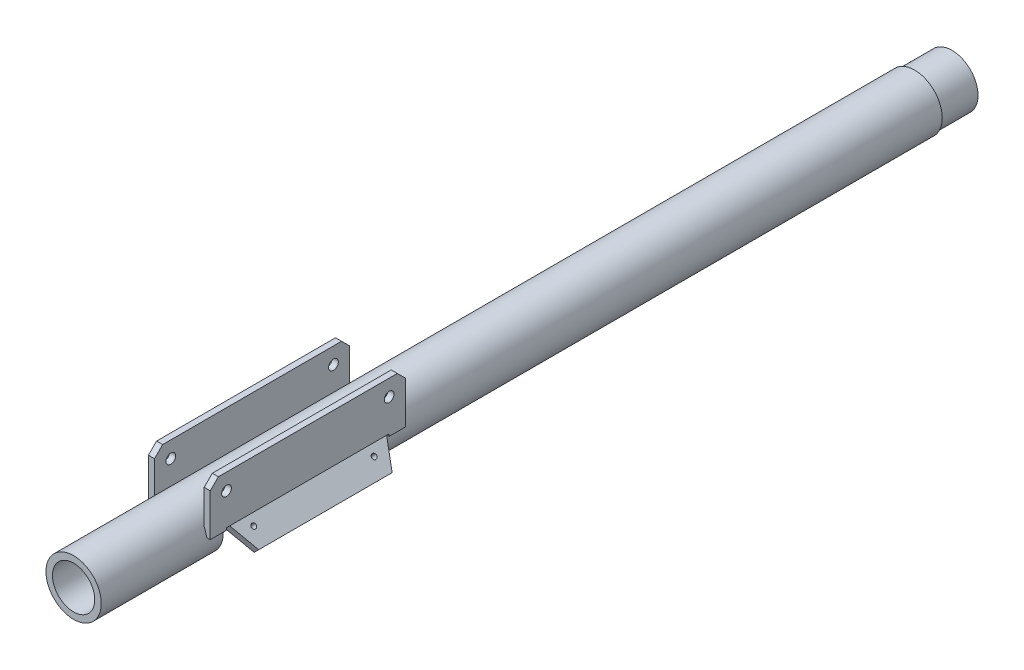
SolidWorks part; units mm, degrees
ref_plane "Front Plane" through (0, 0, 0) normal (0, 0, 1) x (1, 0, 0)
ref_plane "Top Plane" through (0, 0, 0) normal (0, 1, 0) x (1, 0, 0)
ref_plane "Right Plane" through (0, 0, 0) normal (1, 0, 0) x (0, 0, -1)
sketch "Sketch1" plane through (0, 0, 0) normal (0, 0, 1) x (1, 0, 0)
  circle A0 centre (0, 0) radius 17
extrude "Outer Barrel Creation" add sketch "Sketch1" against normal blind 540
sketch "Sketch2" plane through (0, 0, 0) normal (0, 0, 1) x (1, 0, 0)
  circle A0 centre (0, 0) radius 13
sketch "Sketch4" plane through (0, 0, 0) normal (1, 0, 0) x (0, 0, -1)
  line L0 (0, -17) -> (540, -17) construction
  line L1 (75, -17) -> (175, -17)
  line L2 (75, -17) -> (75, 2)
  line L3 (75, 2) -> (175, 2)
  line L4 (175, -17) -> (175, 2)
  line L5 (0, 17) -> (0, -17) construction
  line L6 (540, -17) -> (540, 17) construction
  line L7 (540, 17) -> (0, 17) construction
  point P8 (175, -7.5)
  dimension "D1" = 75
  dimension "D2" = 365
  dimension "D3" = 15
extrude "Screw Intake Extrude" cut sketch "Sketch4" along normal through all both and the other way through all
sketch "Sketch6" plane through (0, 0, 0) normal (1, 0, 0) x (0, 0, -1)
  line L0 (175, 2) -> (175, -17) construction
  line L1 (185, 2.4808) -> (65, 2.4808)
  line L2 (185, 2.4808) -> (185, 7.4808)
  line L3 (185, 7.4808) -> (65, 7.4808)
  line L4 (65, 2.4808) -> (65, 7.4808)
  line L5 (75, -17) -> (75, 2) construction
  dimension "D1" = 10
  dimension "D2" = 5
  dimension "D3" = 10
extrude "Parallel Fin Side Extrusion" add sketch "Sketch6" along normal blind 19 and the other way blind 19
sketch "Sketch7" plane through (0, 7.4808, 0) normal (0, 1, 0) x (1, 0, 0)
  line L1 (15.2656, 185) -> (19, 185)
  line L2 (15.2656, 185) -> (15.2656, 65)
  line L3 (15.2656, 65) -> (19, 65)
  line L4 (19, 185) -> (19, 65)
extrude "Parallel Fin Height Side 1" add sketch "Sketch7" along normal blind 26
sketch "Sketch8" plane through (0, 7.4808, 0) normal (0, 1, 0) x (1, 0, 0)
  line L1 (-19, 185) -> (-15.2656, 185)
  line L2 (-19, 185) -> (-19, 65)
  line L3 (-19, 65) -> (-15.2656, 65)
  line L4 (-15.2656, 185) -> (-15.2656, 65)
extrude "Parallel Fin Height Side 2" add sketch "Sketch8" along normal blind 26
sketch "Sketch9" plane through (-19, 0, 0) normal (-1, 0, 0) x (0, 0, 1)
  line L0 (-185, 33.4808) -> (-65, 33.4808) construction
  line L1 (-185, 2.4808) -> (-185, 33.4808) construction
  line L2 (-65, 33.4808) -> (-65, 2.4808) construction
  line L3 (-180, 33.4808) -> (-185, 28.4808)
  line L4 (-70, 33.4808) -> (-65, 28.4808)
  line L5 (-185, 28.4808) -> (-185, 33.4808)
  line L6 (-185, 33.4808) -> (-180, 33.4808)
  line L7 (-65, 28.4808) -> (-65, 33.4808)
  line L8 (-65, 33.4808) -> (-70, 33.4808)
  circle A0 centre (-175, 23.4808) radius 3
  circle A1 centre (-75, 23.4808) radius 3
  dimension "D5" = 6
  dimension "D6" = 6
  dimension "D1" = 10
  dimension "D2" = 10
  dimension "D3" = 10
  dimension "D4" = 10
  dimension "D7" = 5
  dimension "D8" = 5
  dimension "D9" = 5
  dimension "D10" = 5
extrude "Parallel Fin Details" cut sketch "Sketch9" against normal through all
extrude "Inner Barrel Extrusion" cut sketch "Sketch2" against normal through all
sketch "Sketch10" plane through (0, 0, 0) normal (1, 0, 0) x (0, 0, -1)
  line L0 (0, 0) -> (540, 0)
  line L1 (540, -13) -> (540, 13) construction
ref_axis "Axis1" through (0, 0, 0) along (0, 0, -1)
ref_plane "Plane1" through (0, 0, 0) normal (0.7071, 0.7071, 0) x (0, 0, -1)
sketch "Sketch11" plane through (0, 0, 0) normal (0.7071, 0.7071, 0) x (0, 0, -1)
  line L0 (175, 13.3515) -> (175, -17) construction
  line L1 (175, 12.1583) -> (75, 12.1583)
  line L2 (175, 12.1583) -> (175, 16.1583)
  line L3 (175, 16.1583) -> (75, 16.1583)
  line L4 (75, 12.1583) -> (75, 16.1583)
  line L5 (75, -17) -> (75, 13.3515) construction
  dimension "D1" = 0
  dimension "D2" = 0
  dimension "D3" = 4
extrude "Boss-Extrude6" add sketch "Sketch11" against normal blind 26
sketch "Sketch12" plane through (-11.4256, 11.4256, 0) normal (-0.7071, 0.7071, 0) x (0, 0, 1)
  line L0 (-175, -26) -> (-75, -26) construction
  line L3 (-175, -7.4682) -> (-166, -26)
  line L4 (-175, -26) -> (-175, -10.7118) construction
  line L5 (-166, -26) -> (-175, -26)
  line L6 (-175, -26) -> (-175, -7.4682)
  line L7 (-75, -6.4644) -> (-75, -26)
  line L8 (-75, -26) -> (-75, -10.7118) construction
  line L9 (-75, -26) -> (-84, -26)
  line L10 (-84, -26) -> (-75, -6.4644)
  circle A0 centre (-162, -16) radius 1.5
  circle A1 centre (-88, -16) radius 1.5
  dimension "D3" = 3
  dimension "D4" = 3
  dimension "D1" = 10
  dimension "D2" = 10
  dimension "D5" = 13
  dimension "D6" = 13
  dimension "D7" = 9
  dimension "D8" = 9
extrude "Cut-Extrude5" cut sketch "Sketch12" against normal blind 4
mirror "Mirror2" about plane through (0, 0, 0) normal (1, 0, 0) of "Cut-Extrude5", "Boss-Extrude6"
sketch "Sketch13" plane through (0, 0, -540) normal (0, 0, -1) x (-1, 0, 0)
  circle A0 centre (0, 0) radius 16
  circle A1 centre (0, 0) radius 27.0991
  dimension "D1" = 54.1981
  dimension "D2" = 32
extrude "Cut-Extrude8" cut sketch "Sketch13" against normal blind 23 contours A1 | A0
sketch "Sketch14" plane through (0, 0, -540) normal (0, 0, -1) x (-1, 0, 0)
  point P0 (0, 0)
